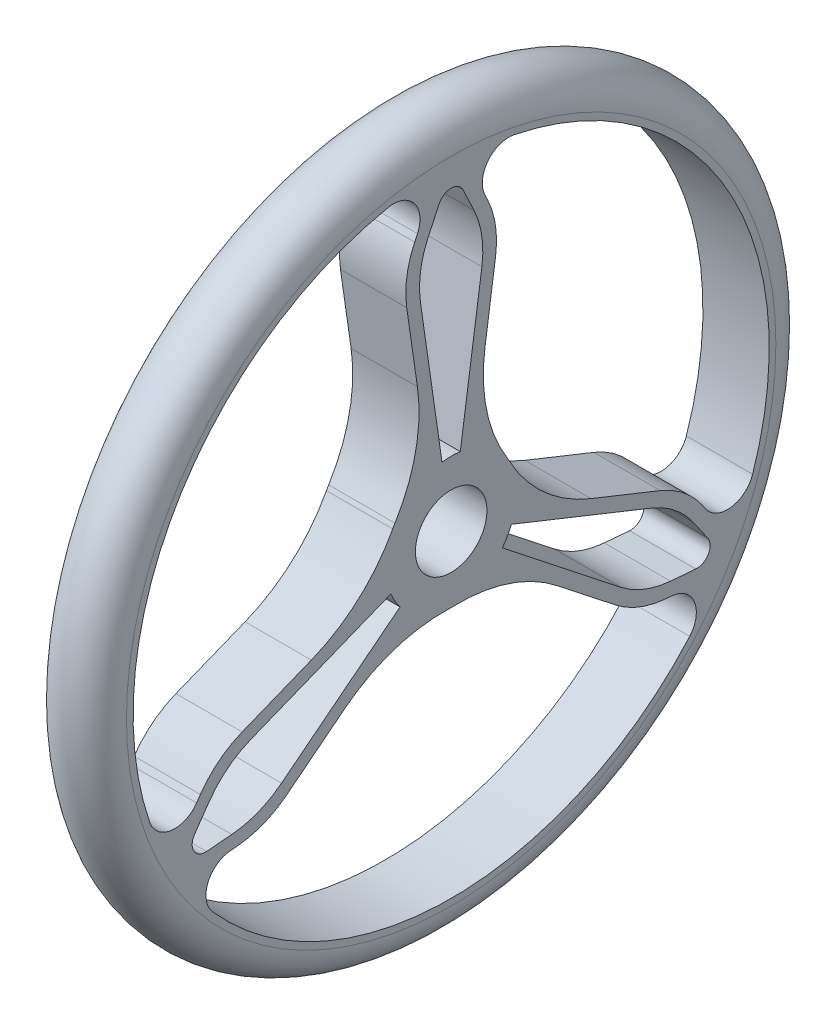
SolidWorks part; units mm, degrees
ref_plane "Front Plane" through (0, 0, 0) normal (0, 0, 1) x (1, 0, 0)
ref_plane "Top Plane" through (0, 0, 0) normal (0, 1, 0) x (1, 0, 0)
ref_plane "Right Plane" through (0, 0, 0) normal (1, 0, 0) x (0, 0, -1)
sketch "Sketch1" plane through (0, 0, 0) normal (1, 0, 0) x (0, 0, -1)
  circle A0 centre (0, 0) radius 270
  circle A1 centre (0, 0) radius 240
extrude "Boss-Extrude1" add sketch "Sketch1" along normal blind 50
fillet "Fillet1" 2 edges at (50, 0, -270) (0, 0, -270) type full round first side face at (50, 0, -270) second side face at (0, 0, -270) middle face at (50, 0, -270)
sketch "Sketch2" plane through (0, 0, 0) normal (1, 0, 0) x (0, 0, -1)
  line L0 (0, 0) -> (0, 240) construction
  line L1 (0, 0) -> (10, 0) construction
  line L2 (10.9102, 6.299) -> (36.525, 183.5734)
  line L3 (36.525, 183.5734) -> (10, 239.7916)
  line L4 (-36.525, 183.5734) -> (-10, 239.7916)
  line L5 (-10.9102, 6.299) -> (-36.525, 183.5734)
  line L6 (177.2417, -60.1552) -> (212.6656, -111.2355)
  line L7 (140.7167, -123.4182) -> (202.6656, -128.556)
  line L8 (0, -12.598) -> (140.7167, -123.4182)
  line L9 (10.9102, 6.299) -> (177.2417, -60.1552)
  line L10 (-140.7167, -123.4182) -> (-202.6656, -128.556)
  line L11 (-177.2417, -60.1552) -> (-212.6656, -111.2355)
  line L12 (-10.9102, 6.299) -> (-177.2417, -60.1552)
  line L13 (0, -12.598) -> (-140.7167, -123.4182)
  arc A0 (-212.6656, -111.2355) -> (-202.6656, -128.556) centre (0, 0) ccw
  arc A1 (202.6656, -128.556) -> (212.6656, -111.2355) centre (0, 0) ccw
  arc A2 (10, 239.7916) -> (-10, 239.7916) centre (0, 0) ccw
  point P24 (0, 0)
  dimension "D1" = 3
extrude "Boss-Extrude2" add sketch "Sketch2" along normal blind 50
sketch "Sketch3" plane through (50, 0, 0) normal (1, 0, 0) x (0, 0, -1)
  circle A0 centre (0, 0) radius 50
extrude "Boss-Extrude3" add sketch "Sketch3" against normal blind 50
sketch "Sketch4" plane through (50, 0, 0) normal (1, 0, 0) x (0, 0, -1)
  circle A0 centre (0, 0) radius 27
extrude "Cut-Extrude1" cut sketch "Sketch4" against normal blind 50
sketch "Sketch5" plane through (50, 0, 0) normal (1, 0, 0) x (0, 0, -1)
  line L2 (-6.9072, 48.5216) -> (-26.1976, 182.0265)
  line L5 (-26.1976, 182.0265) -> (-0.9561, 235.5245)
  line L6 (0.9561, 235.5245) -> (26.1976, 182.0265)
  line L7 (26.1976, 182.0265) -> (6.9072, 48.5216)
  line L8 (-0.9561, 235.5245) -> (0, 237.5509)
  line L9 (0.9561, 235.5245) -> (0, 237.5509)
  line L10 (45.4745, -18.279) -> (170.7384, -68.3255)
  line L11 (144.5408, -113.7011) -> (38.5674, -30.2426)
  line L12 (203.4921, -118.5903) -> (144.5408, -113.7011)
  line L13 (170.7384, -68.3255) -> (204.4482, -116.9342)
  line L14 (203.4921, -118.5903) -> (205.7251, -118.7755)
  line L15 (204.4482, -116.9342) -> (205.7251, -118.7755)
  line L16 (-38.5674, -30.2426) -> (-144.5408, -113.7011)
  line L17 (-170.7384, -68.3255) -> (-45.4745, -18.279)
  line L18 (-204.4482, -116.9342) -> (-170.7384, -68.3255)
  line L19 (-144.5408, -113.7011) -> (-203.4921, -118.5903)
  line L20 (-204.4482, -116.9342) -> (-205.7251, -118.7755)
  line L21 (-203.4921, -118.5903) -> (-205.7251, -118.7755)
  circle A0 centre (0, 0) radius 27
  arc A1 (6.9072, 48.5216) -> (-6.9072, 48.5216) centre (0, 0) ccw
  arc A2 (38.5674, -30.2426) -> (45.4745, -18.279) centre (0, 0) ccw
  arc A3 (-45.4745, -18.279) -> (-38.5674, -30.2426) centre (0, 0) ccw
  point P37 (0, 0)
  dimension "D2" = 3
extrude "Cut-Extrude2" cut sketch "Sketch5" against normal blind 50
fillet "Fillet2" radius 120 1 edges at (25, -38.0988, -32.3803) type face fillet first side face at (25, -44.0494, 0) second side face at (25, -80.7585, -86.5485)
fillet "Fillet3" radius 120 1 edges at (25, -8.9928, -49.1847) type face fillet first side face at (25, 22.0247, -38.1479) second side face at (25, -34.574, -113.2132)
fillet "Fillet4" radius 120 1 edges at (25, -38.0988, 32.3803) type face fillet first side face at (25, -80.7585, 86.5485) second side face at (25, -45.6261, 15.8933)
fillet "Fillet5" radius 120 1 edges at (25, -8.9928, 49.1847) type face fillet first side face at (25, -34.574, 113.2132) second side face at (25, 22.0247, 38.1479)
fillet "Fillet6" radius 120 1 edges at (25, 47.0915, 16.8044) type face fillet first side face at (25, 36.5771, 31.5667) second side face at (25, 115.3325, 26.6647)
fillet "Fillet7" radius 120 1 edges at (25, 47.0915, -16.8044) type face fillet first side face at (25, 36.5771, -31.5667) second side face at (25, 115.3325, -26.6647)
fillet "Fillet8" radius 70 1 edges at (25, -123.4182, -140.7167) type face fillet first side face at (25, -99.5226, -110.3747) second side face at (25, -125.9871, -171.6912)
fillet "Fillet9" radius 70 1 edges at (25, -60.1552, -177.2417) type face fillet first side face at (25, -45.826, -141.3765) second side face at (25, -85.6953, -194.9536)
fillet "Fillet10" radius 70 1 edges at (25, -123.4182, 140.7167) type face fillet first side face at (25, -125.9871, 171.6912) second side face at (25, -99.5226, 110.3747)
fillet "Fillet11" radius 70 1 edges at (25, -60.1552, 177.2417) type face fillet first side face at (25, -85.6953, 194.9536) second side face at (25, -45.826, 141.3765)
fillet "Fillet12" radius 70 1 edges at (25, 183.5734, 36.525) type face fillet first side face at (25, 211.6825, 23.2625) second side face at (25, 145.3486, 31.0018)
fillet "Fillet13" radius 70 1 edges at (25, 183.5734, -36.525) type face fillet first side face at (25, 211.6825, -23.2625) second side face at (25, 145.3486, -31.0018)
fillet "Fillet14" radius 70 1 edges at (25, -113.7011, -144.5408) type face fillet first side face at (25, -71.9718, -91.5541) second side face at (25, -116.2383, -175.133)
fillet "Fillet15" radius 70 1 edges at (25, -68.3255, -170.7384) type face fillet first side face at (25, -43.3023, -108.1065) second side face at (25, -93.5505, -188.2318)
fillet "Fillet16" radius 70 1 edges at (25, -68.3255, 170.7384) type face fillet first side face at (25, -43.3023, 108.1065) second side face at (25, -93.5505, 188.2318)
fillet "Fillet17" radius 70 1 edges at (25, -113.7011, 144.5408) type face fillet first side face at (25, -116.2383, 175.133) second side face at (25, -71.9718, 91.5541)
fillet "Fillet18" radius 70 1 edges at (25, 182.0265, -26.1976) type face fillet first side face at (25, 209.7887, -13.0988) second side face at (25, 115.2741, -16.5524)
fillet "Fillet19" radius 70 1 edges at (25, 182.0265, 26.1976) type face fillet first side face at (25, 115.2741, 16.5524) second side face at (25, 209.7887, 13.0988)
fillet "Fillet20" radius 20 1 edges at (25, 239.7916, -10) type face fillet first side face at (25, 221.2034, -18.7703) second side face at (25, 92.139, -159.5894)
fillet "Fillet21" radius 20 1 edges at (25, 239.7916, 10) type face fillet first side face at (25, 221.2034, 18.7703) second side face at (25, 92.139, 159.5894)
fillet "Fillet22" radius 20 1 edges at (25, -111.2355, -212.6656) type face fillet first side face at (25, -94.3461, -200.9529) second side face at (25, 82.6521, -173.3483)
fillet "Fillet23" radius 20 1 edges at (25, -128.556, -202.6656) type face fillet first side face at (25, -184.278, 0) second side face at (25, -126.8573, -182.1826)
fillet "Fillet24" radius 20 1 edges at (25, -128.556, 202.6656) type face fillet first side face at (25, -191.4501, 15.0954) second side face at (25, -126.8573, 182.1826)
fillet "Fillet25" radius 20 1 edges at (25, -111.2355, 212.6656) type face fillet first side face at (25, -94.3461, 200.9529) second side face at (25, 82.6521, 173.3483)
fillet "Fillet26" radius 10 1 edges at (25, -118.7755, -205.7251) type face fillet first side face at (25, -117.1084, -185.6244) second side face at (25, -102.2012, -194.231)
fillet "Fillet27" radius 10 1 edges at (25, -118.7755, 205.7251) type face fillet first side face at (25, -102.2012, 194.231) second side face at (25, -117.1084, 185.6244)
fillet "Fillet28" radius 10 1 edges at (25, 237.5509, 0) type face fillet first side face at (25, 219.3096, 8.6066) second side face at (25, 219.3096, -8.6066)
